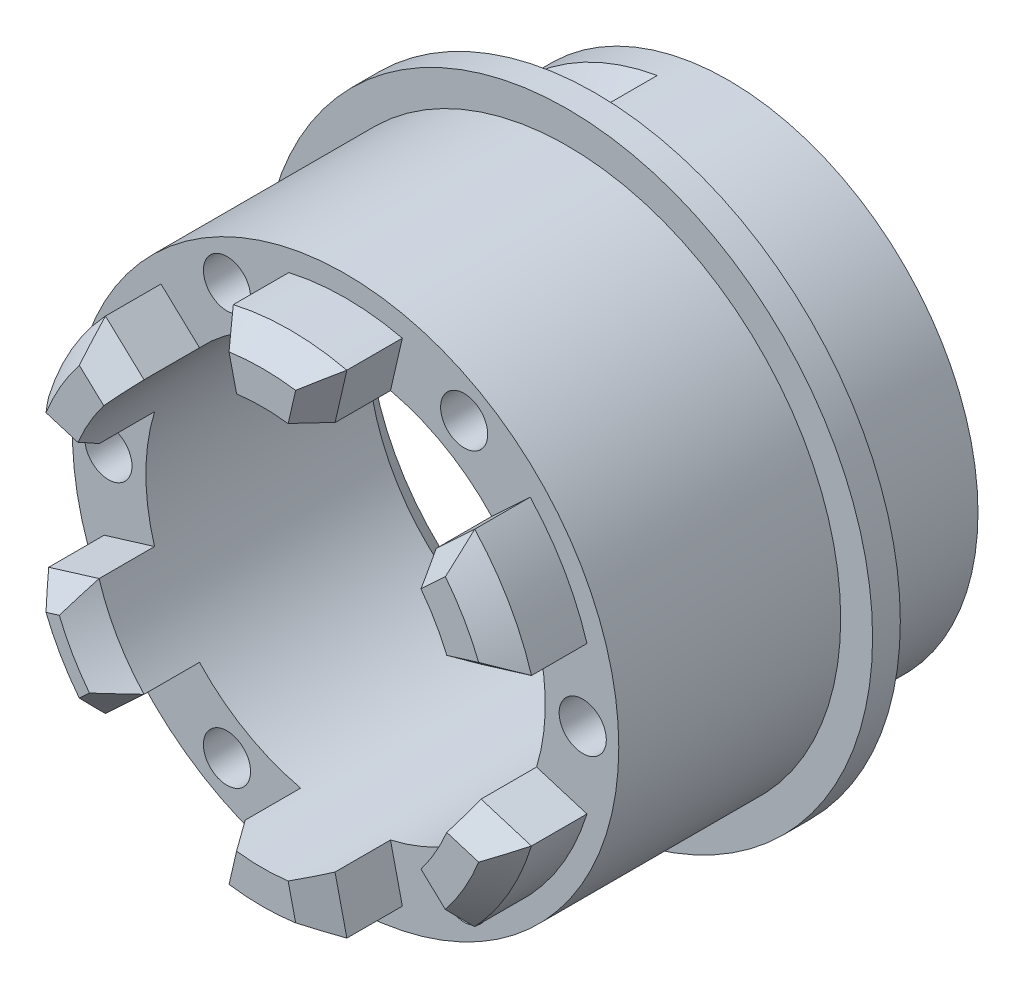
SolidWorks part; units mm, degrees
ref_plane "정면" through (0, 0, 0) normal (0, 0, 1) x (1, 0, 0)
ref_plane "윗면" through (0, 0, 0) normal (0, 1, 0) x (1, 0, 0)
ref_plane "우측면" through (0, 0, 0) normal (1, 0, 0) x (0, 0, -1)
sketch "스케치1" plane through (0, 0, 0) normal (0, 0, 1) x (1, 0, 0)
  circle A0 centre (0, 0) radius 9
  dimension "D1" = 18
extrude "보스-돌출1" add sketch "스케치1" along normal blind 2
sketch "스케치2" plane through (0, 0, 2) normal (0, 0, 1) x (1, 0, 0)
  circle A0 centre (0, 0) radius 9
  circle A1 centre (0, 0) radius 7.2
  circle A5 centre (0, 0) radius 9 construction
  dimension "D1" = 1.8
extrude "보스-돌출2" add sketch "스케치2" along normal blind 2.8
sketch "스케치4" plane through (0, 0, 4.8) normal (0, 0, 1) x (1, 0, 0)
  circle A0 centre (0, 0) radius 11
  circle A1 centre (0, 0) radius 7.2
  circle A2 centre (0, 0) radius 7.2 construction
  dimension "D1" = 22
extrude "보스-돌출3" add sketch "스케치4" along normal blind 1
sketch "스케치5" plane through (0, 0, 5.8) normal (0, 0, 1) x (1, 0, 0)
  circle A0 centre (0, 0) radius 7.2
  circle A1 centre (0, 0) radius 9.85
  circle A2 centre (0, 0) radius 7.2 construction
  dimension "D1" = 19.7
extrude "보스-돌출4" add sketch "스케치5" along normal blind 8
sketch "스케치6" plane through (0, 0, 13.8) normal (0, 0, 1) x (1, 0, 0)
  circle A0 centre (0, 0) radius 8.55 construction
  circle A6 centre (0, 0) radius 7.2 construction
  circle A8 centre (8.55, 0) radius 0.85
  circle A9 centre (4.275, -7.4045) radius 0.85
  circle A10 centre (-4.275, -7.4045) radius 0.85
  circle A11 centre (-8.55, 0) radius 0.85
  circle A12 centre (-4.275, 7.4045) radius 0.85
  circle A13 centre (4.275, 7.4045) radius 0.85
  point P19 (0, 0)
  point P20 (0, 0)
  dimension "D1" = 1.35
  dimension "D2" = 1.7
  dimension "D3" = 6
extrude "컷-돌출1" cut sketch "스케치6" against normal blind 8
sketch "스케치7" plane through (0, 0, 0) normal (0, 0, -1) x (-1, 0, 0)
  circle A0 centre (0, 0) radius 6 construction
  circle A5 centre (0, 0) radius 3
  circle A6 centre (-6, 0) radius 1.1
  circle A7 centre (6, 0) radius 1.1
  circle A9 centre (0, 6) radius 1.1
  circle A11 centre (0, -6) radius 1.1
  dimension "D1" = 12
  dimension "D2" = 2.2
  dimension "D4" = 6
extrude "컷-돌출2" cut sketch "스케치7" against normal through all
sketch "스케치10" plane through (0, 0, 13.8) normal (0, 0, 1) x (1, 0, 0)
  line L24 (2.0471, 8.8668) -> (1.6196, 7.0155)
  line L25 (-2.0471, 8.8668) -> (-1.6196, 7.0155)
  line L26 (6.6553, 6.2062) -> (5.2657, 4.9104)
  line L27 (8.7024, 2.6606) -> (6.8854, 2.1051)
  line L28 (8.7024, -2.6606) -> (6.8854, -2.1051)
  line L29 (6.6553, -6.2062) -> (5.2657, -4.9104)
  line L30 (2.0471, -8.8668) -> (1.6196, -7.0155)
  line L31 (-2.0471, -8.8668) -> (-1.6196, -7.0155)
  line L32 (-6.6553, -6.2062) -> (-5.2657, -4.9104)
  line L33 (-8.7024, -2.6606) -> (-6.8854, -2.1051)
  line L34 (-8.7024, 2.6606) -> (-6.8854, 2.1051)
  line L35 (-6.6553, 6.2062) -> (-5.2657, 4.9104)
  arc A0 (-6.6553, 6.2062) -> (-8.7024, 2.6606) centre (0, 0) ccw
  arc A1 (-6.8854, -2.1051) -> (-5.2657, -4.9104) centre (0, 0) ccw
  arc A2 (2.0471, 8.8668) -> (-2.0471, 8.8668) centre (0, 0) ccw
  arc A3 (8.7024, 2.6606) -> (6.6553, 6.2062) centre (0, 0) ccw
  arc A4 (6.6553, -6.2062) -> (8.7024, -2.6606) centre (0, 0) ccw
  arc A5 (-2.0471, -8.8668) -> (2.0471, -8.8668) centre (0, 0) ccw
  arc A6 (-8.7024, -2.6606) -> (-6.6553, -6.2062) centre (0, 0) ccw
  arc A7 (-1.6196, -7.0155) -> (1.6196, -7.0155) centre (0, 0) ccw
  arc A8 (5.2657, -4.9104) -> (6.8854, -2.1051) centre (0, 0) ccw
  arc A9 (6.8854, 2.1051) -> (5.2657, 4.9104) centre (0, 0) ccw
  arc A10 (1.6196, 7.0155) -> (-1.6196, 7.0155) centre (0, 0) ccw
  arc A11 (-5.2657, 4.9104) -> (-6.8854, 2.1051) centre (0, 0) ccw
  circle A12 centre (0, 0) radius 7.2 construction
  circle A17 centre (0, 0) radius 7.2 construction
  point P9 (0, 0)
  point P10 (0, 0)
  point P21 (0, 0)
  point P30 (0, 0)
  point P48 (0, 0)
  point P61 (0, 0)
  dimension "D1" = 1.9
  dimension "D4" = 6
extrude "보스-돌출5" add sketch "스케치10" along normal blind 3
chamfer "모따기1" distance 1 angle 35 19 edges at (-7.8808, -4.55, 16.8) (0, -9.1, 16.8) (7.8808, -4.55, 16.8) (7.8808, 4.55, 16.8) (0, 9.1, 16.8) (-7.8808, 4.55, 16.8) (-7.7939, -2.3828, 16.8) (-6.2354, -3.6, 16.8) (-5.9605, -5.5583, 16.8) (1.8334, -7.9411, 16.8) (-1.8334, -7.9411, 16.8) (5.9605, -5.5583, 16.8) (7.7939, -2.3828, 16.8) (7.7939, 2.3828, 16.8) (5.9605, 5.5583, 16.8) (1.8334, 7.9411, 16.8) (-1.8334, 7.9411, 16.8) (-7.7939, 2.3828, 16.8) (-5.9605, 5.5583, 16.8) first distance on face at (-7.7798, -4.4917, 15.3) first distance on face at (0, -8.9834, 15.3) first distance on face at (7.7798, -4.4917, 15.3) first distance on face at (7.7798, 4.4917, 15.3) first distance on face at (0, 8.9834, 15.3) first distance on face at (-7.7798, 4.4917, 15.3) first distance on face at (-7.7939, -2.3828, 15.3) first distance on face at (7.2, 0, 2) first distance on face at (-5.9605, -5.5583, 15.3) first distance on face at (1.8334, -7.9411, 15.3) first distance on face at (-1.8334, -7.9411, 15.3) first distance on face at (5.9605, -5.5583, 15.3) first distance on face at (7.7939, -2.3828, 15.3) first distance on face at (7.7939, 2.3828, 15.3) first distance on face at (5.9605, 5.5583, 15.3) first distance on face at (1.8334, 7.9411, 15.3) first distance on face at (-1.8334, 7.9411, 15.3) first distance on face at (-7.7939, 2.3828, 15.3) first distance on face at (-5.9605, 5.5583, 15.3)
sketch "스케치11" plane through (0, 0, 0) normal (0, 0, -1) x (-1, 0, 0)
  line L0 (0, 0) -> (1.7365, 9.8481)
  line L1 (0, 0) -> (1.7365, -9.8481)
  line L2 (0, 0) -> (10, 0) construction
  circle A0 centre (0, 0) radius 10
  circle M6 centre (6, 0) radius 1.1
  circle M9 centre (0, 0) radius 3
  circle M10 centre (0, 0) radius 9
  dimension "D1" = 80
  dimension "D2" = 80
extrude "컷-돌출3" cut sketch "스케치11" against normal blind 2.8 from offset 2 contours L2 A0 L0 M9 M6 | L2 L1 M9 M10 M6 region at (-4.5289, 3.9797, 0) region at (-4.5289, -3.9797, 0) offset against normal yes
chamfer "모따기2" distance 1 angle 45 2 edges at (-7.2, 0, 4.8) (-9, 0, 2)
